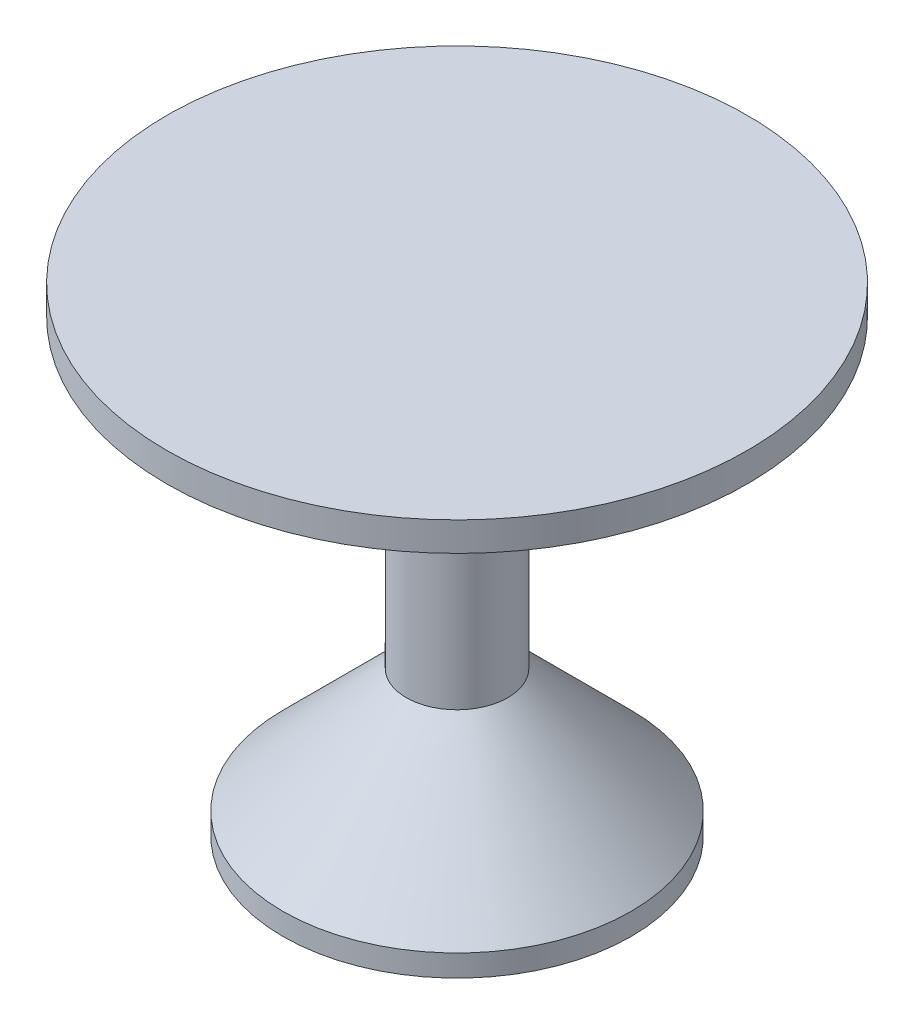
SolidWorks part; units mm, degrees
ref_plane "前视基准面" through (0, 0, 0) normal (0, 0, 1) x (1, 0, 0)
ref_plane "上视基准面" through (0, 0, 0) normal (0, 1, 0) x (1, 0, 0)
ref_plane "右视基准面" through (0, 0, 0) normal (1, 0, 0) x (0, 0, -1)
other "Configuration Table"
sketch "草图1" plane through (0, 0, 0) normal (0, 1, 0) x (1, 0, 0)
  circle A0 centre (0, 0) radius 24.5
  dimension "D1" = 49
extrude "凸台-拉伸1" add sketch "草图1" along normal blind 4
sketch "q" plane through (0, 4, 0) normal (0, 1, 0) x (1, 0, 0)
  circle A0 centre (0, 0) radius 60
  dimension "D1" = 120
extrude "凸台-拉伸2" add sketch "q" along normal blind 5
sketch "草图3" plane through (0, 9, 0) normal (0, 1, 0) x (1, 0, 0)
  circle A0 centre (0, 0) radius 17.5
  dimension "D1" = 35
extrude "凸台-拉伸3" add sketch "草图3" along normal blind 150
sketch "草图4" plane through (0, 159, 0) normal (0, 1, 0) x (1, 0, 0)
  circle A0 centre (0, 0) radius 100
  dimension "D1" = 200
extrude "凸台-拉伸4" add sketch "草图4" along normal blind 10
chamfer "倒角1" distance 45 angle 45 1 edges at (0, 9, 17.5)
chamfer "倒角2" distance 30 angle 60 1 edges at (0, 159, 17.5) first distance on face at (0, 54, 17.5)
